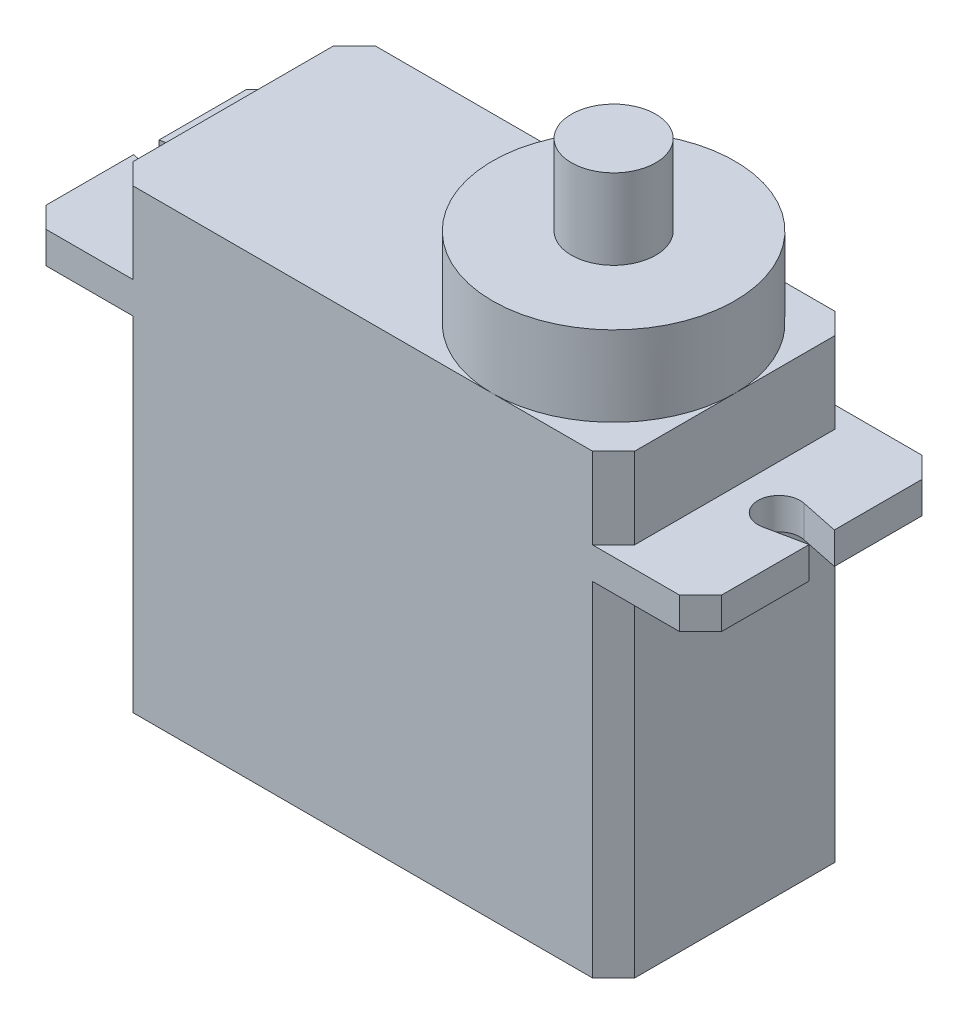
SolidWorks part; units mm, degrees
ref_plane "Front Plane" through (0, 0, 0) normal (0, 0, 1) x (1, 0, 0)
ref_plane "Top Plane" through (0, 0, 0) normal (0, 1, 0) x (1, 0, 0)
ref_plane "Right Plane" through (0, 0, 0) normal (1, 0, 0) x (0, 0, -1)
sketch "Sketch1" plane through (0, 0, 0) normal (0, 1, 0) x (1, 0, 0)
  line L0 (0, 0) -> (-14, 0) construction
  line L1 (-10.9, -5.75) -> (10.9, -5.75)
  line L2 (-16.025, -4.75) -> (-16.025, -0.6)
  line L3 (-10.9, 5.75) -> (10.9, 5.75)
  line L4 (16.025, -4.75) -> (16.025, -0.6)
  line L5 (-16.025, -5.75) -> (16.025, 5.75) construction
  line L6 (-16.025, 5.75) -> (16.025, -5.75) construction
  line L7 (0, 0) -> (14, 0) construction
  line L8 (-11.9, 0) -> (11.9, 0)
  line L9 (11.9, 4.75) -> (11.9, -4.75)
  line L10 (-11.9, 4.75) -> (-11.9, -4.75)
  line L11 (11.9, 0) -> (6.15, 0) construction
  line L12 (16.025, 0.6) -> (16.025, 4.75)
  line L13 (-16.025, 4.75) -> (-15.025, 5.75)
  line L14 (14.2037, 0.979) -> (16.025, 0.6)
  line L15 (14.2037, -0.979) -> (16.025, -0.6)
  line L16 (-14.2037, 0.979) -> (-16.025, 0.6)
  line L17 (-14.2037, -0.979) -> (-16.025, -0.6)
  line L18 (-16.025, 0.6) -> (-16.025, 4.75)
  line L19 (16.025, 4.75) -> (15.025, 5.75)
  line L20 (15.025, -5.75) -> (16.025, -4.75)
  line L21 (-15.025, -5.75) -> (-16.025, -4.75)
  line L22 (-10.9, 5.75) -> (-11.9, 4.75)
  line L23 (-11.9, -4.75) -> (-10.9, -5.75)
  line L24 (11.9, -4.75) -> (10.9, -5.75)
  line L25 (10.9, 5.75) -> (11.9, 4.75)
  line L26 (-15.025, 5.75) -> (15.025, 5.75)
  line L27 (15.025, -5.75) -> (-15.025, -5.75)
  line L28 (6.15, 2) -> (6.0603, 1.7477)
  line L30 (6.2397, 1.7477) -> (6.15, 2)
  arc A0 (-14.2037, -0.979) -> (-14.2037, 0.979) centre (-14, 0) ccw
  arc A1 (14.2037, 0.979) -> (14.2037, -0.979) centre (14, 0) ccw
  circle A2 centre (6.15, 0) radius 5.75
  circle A3 centre (6.15, 0) radius 2
  point P0 (0, 0)
  point P11 (11.9, 5.75)
  point P14 (0, 0)
  point P15 (11.9, -5.75)
  point P16 (-11.9, 5.75)
  point P17 (-11.9, -5.75)
  point P23 (-16.025, 0)
  point P26 (16.025, 0)
extrude "Boss-Extrude1" add sketch "Sketch1" along normal blind 21.65 contours L3 L25 L9 L24 L1 L23 L10 L22
extrude "Boss-Extrude2" add sketch "Sketch1<3>" along normal blind 25.45 contours A2
sketch "Sketch1<3>" plane through (0, 0, 0) normal (0, 1, 0) x (1, 0, 0) same geometry as "Sketch1"
extrude "Boss-Extrude3" add sketch "Sketch1<4>" along normal blind 29.25 contours A3
sketch "Sketch1<4>" plane through (0, 0, 0) normal (0, 1, 0) x (1, 0, 0) same geometry as "Sketch1"
extrude "Boss-Extrude4" add sketch "Sketch1<5>" along normal blind 1.5 from offset 16.3 contours A1 L14 L12 L19 L26 L25 L9 L24 L27 L20 L4 L15 | A0 L17 L2 L21 L27 L23 L10 L22 L26 L13 L18 L16 region at (-12.9625, 0, 5.6241) region at (11.489, 0, 5.339)
sketch "Sketch1<5>" plane through (0, 0, 0) normal (0, 1, 0) x (1, 0, 0) same geometry as "Sketch1"
